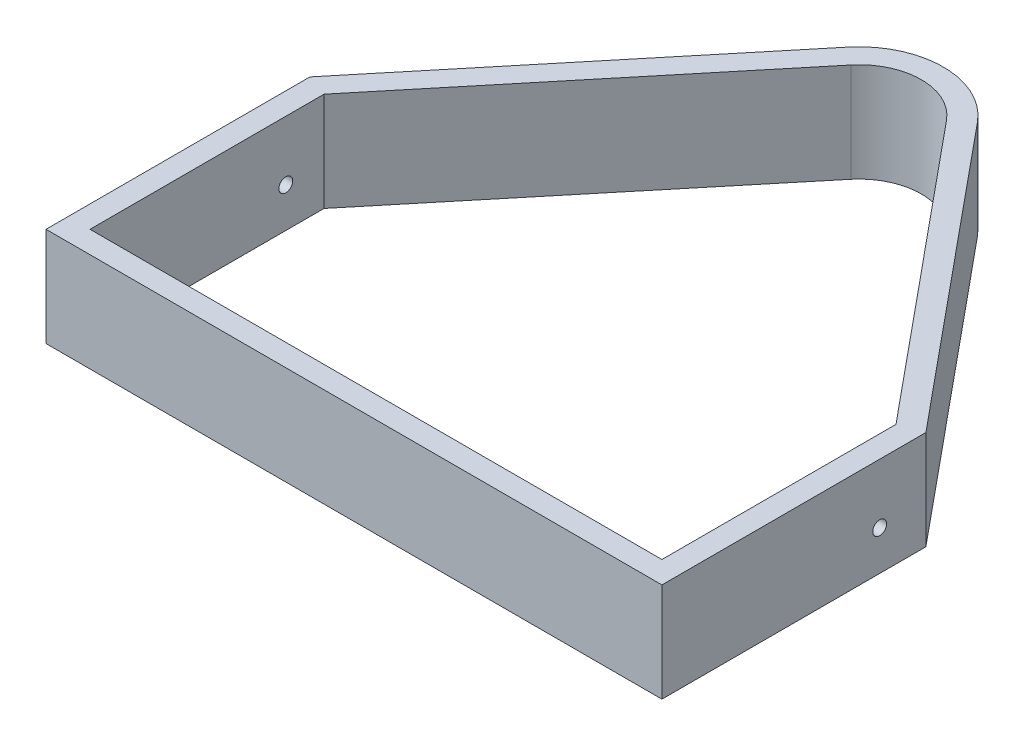
SolidWorks part; units mm, degrees
ref_plane "Front Plane" through (0, 0, 0) normal (0, 0, 1) x (1, 0, 0)
ref_plane "Top Plane" through (0, 0, 0) normal (0, 1, 0) x (1, 0, 0)
ref_plane "Right Plane" through (0, 0, 0) normal (1, 0, 0) x (0, 0, -1)
sketch "Sketch1" plane through (0, 0, 0) normal (0, 1, 0) x (1, 0, 0)
  line L0 (-88.9, 0) -> (88.9, 0)
  line L1 (-88.9, 38.1) -> (88.9, 38.1) construction
  line L2 (-88.9, 0) -> (-88.9, 76.2)
  line L3 (-88.9, 38.1) -> (0, 145.8631) construction
  line L8 (0, 145.8631) -> (88.9, 38.1) construction
  line L13 (88.9, 0) -> (88.9, 76.2)
  line L14 (-88.9, 76.2) -> (-18.7027, 161.292)
  line L15 (18.7027, 161.292) -> (88.9, 76.2)
  line L16 (-82.55, 6.35) -> (-82.55, 73.9188)
  line L17 (-82.55, 73.9188) -> (-13.8044, 157.2511)
  line L18 (13.8044, 157.2511) -> (82.55, 73.9188)
  line L19 (82.55, 6.35) -> (82.55, 73.9188)
  line L20 (-82.55, 6.35) -> (82.55, 6.35)
  arc A0 (-18.7027, 161.292) -> (18.7027, 161.292) centre (0, 145.8631) cw
  arc A2 (-13.8044, 157.2511) -> (13.8044, 157.2511) centre (0, 145.8631) cw
  point P4 (0, 0)
  dimension "D1" = 177.8
  dimension "D2" = 139.7
  dimension "D3" = 38.1
  dimension "D4" = 76.2
  dimension "D6" = 6.35
extrude "Boss-Extrude1" add sketch "Sketch1" along normal blind 28.575
sketch "Sketch2" plane through (0, 0, 0) normal (1, 0, 0) x (0, 0, -1)
  line L4 (73.9188, 28.575) -> (73.9188, 0) construction
  line L5 (0, 0) -> (76.2, 0) construction
  circle A0 centre (62.8698, 11.43) radius 11.049 construction
  circle A1 centre (62.8698, 11.43) radius 2
  dimension "D1" = 22.098
  dimension "D2" = 4
  dimension "D3" = 11.43
extrude "Cut-Extrude1" cut sketch "Sketch2" against normal up to next from surface starting at face at (-82.55, 14.2875, -40.1344)
extrude "Cut-Extrude3" cut sketch "Sketch2<2>" along normal up to next from surface starting at face at (82.55, 14.2875, -40.1344)
sketch "Sketch2<2>" plane through (0, 0, 0) normal (1, 0, 0) x (0, 0, -1) same geometry as "Sketch2"
